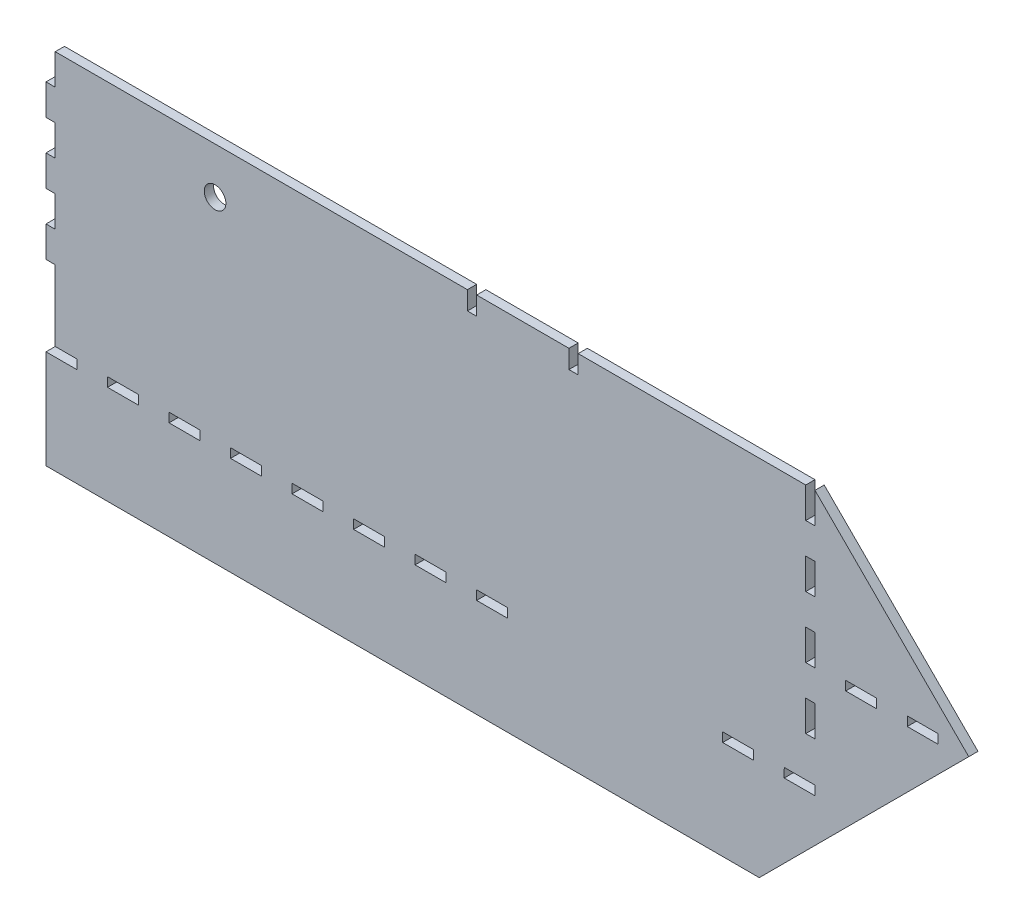
SolidWorks part; units mm, degrees
ref_plane "Front Plane" through (0, 0, 0) normal (0, 0, 1) x (1, 0, 0)
ref_plane "Top Plane" through (0, 0, 0) normal (0, 1, 0) x (1, 0, 0)
ref_plane "Right Plane" through (0, 0, 0) normal (1, 0, 0) x (0, 0, -1)
sketch "Sketch1" plane through (0, 0, 0) normal (0, 0, 1) x (1, 0, 0)
  line L0 (-112.631, -63.8403) -> (-112.631, -53.7284)
  line L1 (134.369, 32.2716) -> (60.379, 32.2716)
  line L2 (-72.631, -50.7284) -> (-62.631, -50.7284)
  line L3 (-62.631, 32.2716) -> (24.379, 32.2716)
  line L4 (137.369, 32.2716) -> (187.369, -17.7284)
  line L5 (187.369, -17.7284) -> (137.369, -67.7284)
  line L6 (-112.631, 17.2716) -> (-57.6695, 17.2716) construction
  line L7 (42.379, 32.2716) -> (27.379, 32.2716)
  line L8 (27.379, 32.2716) -> (27.379, 26.2716)
  line L9 (137.369, 32.2716) -> (137.369, -67.7284) construction
  line L10 (137.369, -17.7284) -> (187.369, -17.7284) construction
  line L11 (157.369, -16.2284) -> (147.369, -16.2284)
  line L12 (177.369, -16.2284) -> (167.369, -16.2284)
  line L13 (177.369, -16.2284) -> (177.369, -19.2284)
  line L14 (177.369, -19.2284) -> (167.369, -19.2284)
  line L15 (167.369, -16.2284) -> (167.369, -19.2284)
  line L16 (177.369, -16.2284) -> (167.369, -19.2284) construction
  line L17 (177.369, -19.2284) -> (167.369, -16.2284) construction
  line L18 (157.369, -16.2284) -> (157.369, -19.2284)
  line L19 (157.369, -19.2284) -> (147.369, -19.2284)
  line L20 (147.369, -16.2284) -> (147.369, -19.2284)
  line L21 (137.3812, -50.7284) -> (127.3812, -50.7284)
  line L22 (137.3812, -50.7284) -> (137.3692, -53.7284)
  line L23 (137.3692, -53.7284) -> (127.3692, -53.7284)
  line L24 (127.3812, -50.7284) -> (127.3692, -53.7284)
  line L25 (137.3812, -50.7284) -> (127.3692, -53.7284) construction
  line L26 (137.3692, -53.7284) -> (127.3812, -50.7284) construction
  line L27 (117.3811, -50.7284) -> (107.3787, -50.7284)
  line L28 (117.3811, -50.7284) -> (117.3691, -53.7284)
  line L29 (117.3691, -53.7284) -> (107.3691, -53.7284)
  line L30 (107.3787, -50.7284) -> (107.3691, -53.7284)
  line L31 (117.3811, -50.7284) -> (107.3691, -53.7284) construction
  line L32 (117.3691, -53.7284) -> (107.3787, -50.7284) construction
  line L33 (27.379, 26.2716) -> (24.379, 26.2716)
  line L34 (24.379, 26.2716) -> (24.379, 32.2716)
  line L35 (27.379, 32.2716) -> (57.379, 32.2716)
  line L36 (137.369, -67.7284) -> (119.2571, -85.8403)
  line L37 (60.379, 26.2716) -> (60.379, 32.2716)
  line L38 (57.379, 26.2716) -> (60.379, 26.2716)
  line L39 (57.379, 32.2716) -> (57.379, 26.2716)
  line L40 (57.379, 32.2716) -> (42.379, 32.2716)
  line L41 (60.379, 32.2716) -> (134.369, 32.2716)
  line L42 (119.2571, -85.8403) -> (-112.631, -85.8403)
  line L43 (-112.631, -85.8403) -> (-112.631, -63.8403)
  line L51 (37.3714, -50.7284) -> (27.369, -50.7284)
  line L52 (37.3714, -50.7284) -> (37.369, -53.7284)
  line L53 (37.369, -53.7284) -> (27.369, -53.7284)
  line L54 (27.369, -50.7284) -> (27.369, -53.7284)
  line L55 (37.3714, -50.7284) -> (27.369, -53.7284) construction
  line L56 (37.369, -53.7284) -> (27.369, -50.7284) construction
  line L57 (17.369, -50.7284) -> (7.369, -50.7284)
  line L58 (17.369, -50.7284) -> (17.369, -53.7284)
  line L59 (17.369, -53.7284) -> (7.369, -53.7284)
  line L60 (7.369, -50.7284) -> (7.369, -53.7284)
  line L61 (17.369, -50.7284) -> (7.369, -53.7284) construction
  line L62 (17.369, -53.7284) -> (7.369, -50.7284) construction
  line L63 (-2.631, -50.7284) -> (-12.631, -50.7284)
  line L64 (-2.631, -50.7284) -> (-2.631, -53.7284)
  line L65 (-2.631, -53.7284) -> (-12.631, -53.7284)
  line L66 (-12.631, -50.7284) -> (-12.631, -53.7284)
  line L67 (-2.631, -50.7284) -> (-12.631, -53.7284) construction
  line L68 (-2.631, -53.7284) -> (-12.631, -50.7284) construction
  line L69 (-22.631, -50.7284) -> (-32.631, -50.7284)
  line L70 (-22.631, -50.7284) -> (-22.631, -53.7284)
  line L71 (-22.631, -53.7284) -> (-32.631, -53.7284)
  line L72 (-32.631, -50.7284) -> (-32.631, -53.7284)
  line L73 (-22.631, -50.7284) -> (-32.631, -53.7284) construction
  line L74 (-22.631, -53.7284) -> (-32.631, -50.7284) construction
  line L75 (-42.631, -50.7284) -> (-52.631, -50.7284)
  line L76 (-42.631, -50.7284) -> (-42.631, -53.7284)
  line L77 (-42.631, -53.7284) -> (-52.631, -53.7284)
  line L78 (-52.631, -50.7284) -> (-52.631, -53.7284)
  line L79 (-42.631, -50.7284) -> (-52.631, -53.7284) construction
  line L80 (-42.631, -53.7284) -> (-52.631, -50.7284) construction
  line L82 (-62.631, -50.7284) -> (-62.631, -53.7284)
  line L83 (-62.631, -53.7284) -> (-72.631, -53.7284)
  line L84 (-72.631, -50.7284) -> (-72.631, -53.7284)
  line L85 (-62.631, -50.7284) -> (-72.631, -53.7284) construction
  line L86 (-62.631, -53.7284) -> (-72.631, -50.7284) construction
  line L87 (137.369, 12.2716) -> (134.369, 12.2716)
  line L88 (-82.631, -50.7284) -> (-82.631, -53.7284)
  line L89 (-82.631, -53.7284) -> (-92.631, -53.7284)
  line L90 (-92.631, -50.7284) -> (-92.631, -53.7284)
  line L91 (-82.631, -50.7284) -> (-92.631, -53.7284) construction
  line L92 (-82.631, -53.7284) -> (-92.631, -50.7284) construction
  line L94 (-102.631, -50.7284) -> (-102.631, -53.7284)
  line L95 (-102.631, -53.7284) -> (-112.631, -53.7284)
  line L97 (-102.631, -50.7284) -> (-112.631, -53.7284) construction
  line L98 (-102.631, -53.7284) -> (-107.631, -52.2284) construction
  line L99 (-62.631, -50.7284) -> (-72.631, -50.7284) [skipped]
  line L100 (-82.631, -50.7284) -> (-92.631, -50.7284) [skipped]
  line L101 (-102.631, -50.7284) -> (-112.631, -50.7284) [skipped]
  line L102 (137.369, 32.2716) -> (137.369, 22.2716)
  line L103 (137.369, 22.2716) -> (134.369, 22.2716)
  line L104 (134.369, 32.2716) -> (134.369, 22.2716)
  line L105 (137.369, 12.2716) -> (137.369, 2.2716)
  line L106 (137.369, 2.2716) -> (134.369, 2.2716)
  line L107 (134.369, 12.2716) -> (134.369, 2.2716)
  line L108 (137.369, -7.7284) -> (134.369, -7.7284)
  line L109 (137.369, -7.7284) -> (137.369, -17.7284)
  line L111 (137.369, -17.7284) -> (134.369, -17.7284)
  line L114 (157.369, -16.2284) -> (147.369, -19.2284) construction
  line L121 (134.369, -7.7284) -> (134.369, -17.7284)
  line L122 (157.369, -19.2284) -> (147.369, -16.2284) construction
  line L124 (-109.631, -50.7284) -> (-102.631, -50.7284)
  line L125 (-112.631, -52.2284) -> (-112.631, -53.3547) [skipped]
  line L126 (-62.631, 32.2716) -> (-109.631, 32.2716)
  line L127 (-112.631, -7.7284) -> (-109.631, -7.7284)
  line L128 (137.369, -27.7284) -> (134.369, -27.7284)
  line L129 (137.369, -27.7284) -> (137.369, -37.7284)
  line L130 (137.369, -37.7284) -> (134.369, -37.7284)
  line L131 (134.369, -27.7284) -> (134.369, -37.7284)
  line L132 (-112.631, 22.2716) -> (-112.631, 12.2716)
  line L133 (-109.631, -17.7284) -> (-112.631, -17.7284)
  line L134 (-112.631, -27.7284) -> (-109.631, -27.7284)
  line L135 (-109.631, -50.7284) -> (-109.631, -27.7284)
  line L136 (-109.631, 2.2716) -> (-112.631, 2.2716)
  line L137 (-112.631, 2.2716) -> (-112.631, -7.7284)
  line L138 (-109.631, 22.2716) -> (-109.631, 32.2716)
  line L139 (-109.631, 22.2716) -> (-112.631, 22.2716)
  line L140 (-112.631, 12.2716) -> (-109.631, 12.2716)
  line L141 (-109.631, -17.7284) -> (-109.631, -7.7284)
  line L142 (-112.631, -17.7284) -> (-112.631, -27.7284)
  line L143 (-109.631, 2.2716) -> (-109.631, 12.2716)
  line L144 (-92.631, -50.7284) -> (-82.631, -50.7284)
  circle A0 centre (-57.6695, 17.2716) radius 3.5187
  point P5 (172.369, -17.7284)
  point P9 (151.1235, -51.5486)
  point P17 (152.369, -17.7284)
  point P19 (131.1235, -51.6165)
  point P24 (111.1235, -51.6845)
  point P44 (31.1235, -51.9564)
  point P49 (11.1235, -52.0244)
  point P54 (-8.8765, -52.0924)
  point P59 (-28.8765, -52.1604)
  point P64 (-48.8765, -52.2284)
  point P70 (-68.8765, -52.2284)
  point P75 (-88.8765, -52.2284)
  point P80 (-108.8765, -52.2284)
  dimension "D3" = 300
  dimension "D5" = 50
  dimension "D6" = 10
  dimension "D7" = 10
  dimension "D8" = 10
  dimension "D10" = 3
  dimension "D11" = 22
  dimension "D13" = 3
  dimension "D14" = 10
  dimension "D15" = 94.99
  dimension "D17" = 15
  dimension "D18" = 6
  dimension "D19" = 3
  dimension "D21" = 10
  dimension "D22" = 10
  dimension "D23" = 10
  dimension "D24" = 10
  dimension "D25" = 10
  dimension "D26" = 10
  dimension "D9" = 10
  dimension "D27" = 10
  dimension "D28" = 10
  dimension "D29" = 10
  dimension "D30" = 10
  dimension "D31" = 15
  dimension "D38" = 10
  dimension "D39" = 10
  dimension "D40" = 3
  dimension "D41" = 10
  dimension "D20" = 47
  dimension "D42" = 3
  dimension "D12" = 4
  dimension "D16" = 4
extrude "Boss-Extrude1" add sketch "Sketch1" along normal blind 3 contours L94 L95 L0 L5 L4 L3 L82 L83 L84 L88 L89 L90 L24 L21 L22 L23 L30 L27 L28 L29 region at (23.2041, -25.834, 0)
